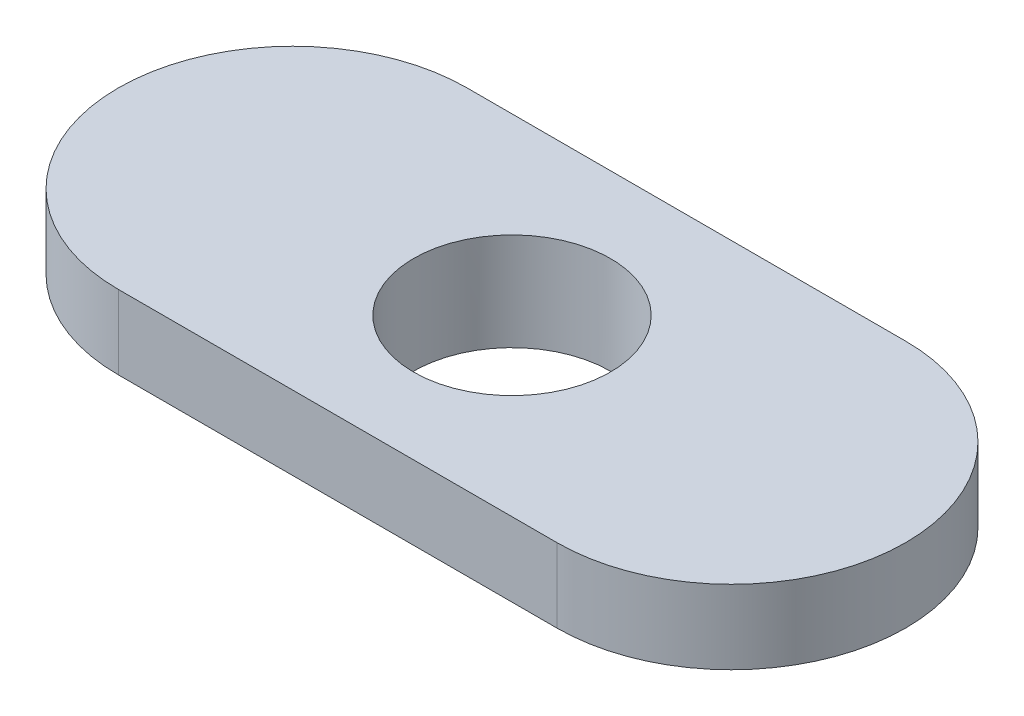
SolidWorks part; units mm, degrees
ref_plane "Front Plane" through (0, 0, 0) normal (0, 0, 1) x (1, 0, 0)
ref_plane "Top Plane" through (0, 0, 0) normal (0, 1, 0) x (1, 0, 0)
ref_plane "Right Plane" through (0, 0, 0) normal (1, 0, 0) x (0, 0, -1)
sketch "Sketch1" plane through (0, 0, 0) normal (0, 1, 0) x (1, 0, 0)
  circle A0 centre (0, 0) radius 3.175
  point P3 (-3.175, 0)
  point P4 (3.175, 0)
  dimension "D1" = 6.35
sketch "Sketch8" plane through (0, 0, 0) normal (0, 1, 0) x (1, 0, 0)
  line L0 (-7.0739, 0) -> (7.0739, 0) construction
  line L1 (-7.0739, 5.6261) -> (7.0739, 5.6261)
  line L2 (-7.0739, -5.6261) -> (7.0739, -5.6261)
  line L4 (-12.7, 5.6261) -> (12.7, 5.6261) construction
  line L5 (-12.7, 5.6261) -> (-12.7, -5.6261) construction
  line L6 (-12.7, -5.6261) -> (12.7, -5.6261) construction
  line L7 (12.7, 5.6261) -> (12.7, -5.6261) construction
  arc A0 (-7.0739, 5.6261) -> (-7.0739, -5.6261) centre (-7.0739, 0) ccw
  arc A1 (7.0739, -5.6261) -> (7.0739, 5.6261) centre (7.0739, 0) ccw
  circle A3 centre (0, 0) radius 3.175
  circle A4 centre (0, 0) radius 3.175
  point P2 (0, 0)
  dimension "D2" = 25.4
  dimension "D3" = 11.2522
  dimension "D1" = 0
extrude "Boss-Extrude2" add sketch "Sketch8" against normal blind 2.3876 from offset 6.35 separate body offset against normal yes
sketch "Sketch9" plane through (0, -8.7376, 0) normal (0, -1, 0) x (1, 0, 0)
  circle A1 centre (0, 0) radius 3.175 construction
  circle A2 centre (0, 0) radius 3.175
  circle A3 centre (0, 0) radius 3.5687
  dimension "D1" = 7.1374
extrude "Boss-Extrude3" add sketch "Sketch9" along normal blind 0.762
extrude "Boss-Extrude1" [suppressed] add sketch "Sketch1" against normal blind 12.7
sketch "Sketch2" [suppressed] plane through (0, -12.7, 0) normal (0, -1, 0) x (1, 0, 0)
  circle A1 centre (0, 0) radius 3.175
  circle A2 centre (0, 0) radius 3.175
  point P0 (0, -3.175)
  dimension "D1" = 0
curve "Helix/Spiral1" [suppressed] pitch 1.27 height 13.97 turns 11
sketch "Sketch3" [suppressed] plane through (0, 0, 0) normal (1, 0, 0) x (0, 0, -1)
  line L0 (3.3125, -12.6206) -> (2.2126, -13.2556) construction
  line L1 (2.2126, -13.2556) -> (3.3125, -13.8906) construction
  line L2 (3.3125, -13.8906) -> (3.3125, -12.6206) construction
  line L3 (2.3501, -13.1762) -> (2.3501, -13.335) construction
  line L4 (3.175, -12.7) -> (3.175, -13.8112) construction
  line L5 (2.2126, -13.2556) -> (2.3501, -13.2556) construction
  line L6 (3.175, -13.2556) -> (3.3125, -13.2556) construction
  line L8 (2.2126, -13.2556) -> (-3.175, -13.2556) construction
  line L9 (2.3501, -13.1762) -> (3.2437, -12.6603)
  line L10 (2.3501, -13.1762) -> (2.3501, -13.335)
  line L11 (2.3501, -13.335) -> (3.2437, -13.8509)
  line L12 (3.2437, -13.8509) -> (3.2437, -12.6603)
  line L14 (-3.175, -13.2556) -> (-3.175, -11.9856) construction
  line L15 (-3.175, -11.9856) -> (-3.175, -10.7156) construction
  line L16 (-3.175, -10.7156) -> (-3.175, -9.4456) construction
  line L17 (-3.175, -9.4456) -> (-3.175, -8.1756) construction
  line L18 (-3.175, 0) -> (-3.175, -12.7) construction
  point P15 (3.2437, -13.2556)
  dimension "D1" = 1.27
  dimension "D2" = 0.1588
sweep "Cut-Sweep1" [suppressed] cut profiles "Sketch3" path "Helix/Spiral1"
sketch "Sketch4" [suppressed] plane through (0, -12.7, 0) normal (0, -1, 0) x (1, 0, 0)
  circle A0 centre (0, 0) radius 2.2126
extrude "Cut-Extrude1" [suppressed] cut sketch "Sketch4" against normal blind 1.27 draft 45 flip side to cut
sketch "Sketch5" [suppressed] plane through (0, 0, 0) normal (0, 0, 1) x (1, 0, 0)
  line L0 (0, 0) -> (0, 3.3528)
  line L1 (-5.5499, 0) -> (0, 0)
  line L2 (0, 3.3528) -> (-3.175, 3.3528)
  line L4 (-5.5499, 0.8382) -> (-5.5499, 0)
  line L5 (0, 0) -> (0, -12.7) construction
  arc A0 (-3.175, 3.3528) -> (-5.5499, 0.8382) centre (0, -2.0246) ccw
  dimension "D1" = 3.3528
  dimension "D2" = 0.8382
  dimension "D4" = 11.0998
revolve "Revolve1" [suppressed] add sketch "Sketch5" angle 360 mid plane about L0
sketch "Sketch6" [suppressed] plane through (0, 3.3528, 0) normal (0, 1, 0) x (1, 0, 0)
  line L1 (0, 2.2914) -> (-1.9844, 1.1457)
  line L2 (-1.9844, 1.1457) -> (-1.9844, -1.1457)
  line L3 (-1.9844, -1.1457) -> (0, -2.2914)
  line L4 (0, -2.2914) -> (1.9844, -1.1457)
  line L5 (1.9844, -1.1457) -> (1.9844, 1.1457)
  line L6 (1.9844, 1.1457) -> (0, 2.2914)
  circle A0 centre (0, 0) radius 1.9844 construction
  dimension "D1" = 3.9688
extrude "Cut-Extrude2" [suppressed] cut sketch "Sketch6" against normal blind 2.3813
sketch "Sketch7" [suppressed] plane through (0, 3.3528, 0) normal (0, 1, 0) x (1, 0, 0)
  circle A0 centre (0, 0) radius 2.2914
extrude "Cut-Extrude3" [suppressed] cut sketch "Sketch7" against normal blind 2.3813 draft 45
sketch "SketchZ" [suppressed] plane through (0, 0, 0) normal (0, 0, 1) x (1, 0, 0)
  line L0 (3.175, -12.9381) -> (3.175, -11.6681) construction
  line L2 (0, -13.2556) -> (0, -11.9856) construction
  line L4 (3.175, -12.9381) -> (0, -12.9381) construction
  line L5 (0, -9.4456) -> (0, -8.1756) construction
  line L6 (0, -12.6206) -> (0, -13.2556) construction
equation "\"D3@Helix/Spiral1\" = \"D4@Helix/Spiral1\" + \"D1@Boss-Extrude1\""
equation "\"D1@Sketch3\" = \"D4@Helix/Spiral1\""
equation "\"D2@Sketch3\" = \"D1@Sketch3\" / 8"
equation "\"D1@Cut-Extrude1\" = \"D4@Helix/Spiral1\""
equation "\"D1@Cut-Extrude2\" = \"D1@Sketch6\" * 3/5"
equation "\"D1@Cut-Extrude3\" = \"D1@Cut-Extrude2\""
equation "\"D2@Sketch5\" = \"D1@Sketch5\" * 1/4"
